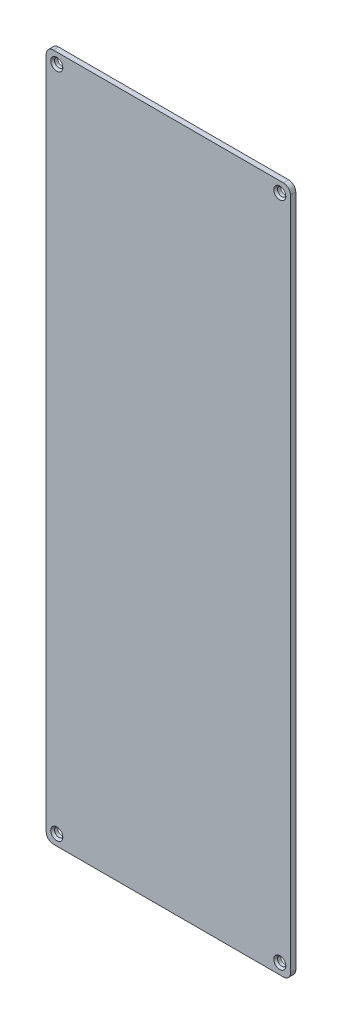
SolidWorks part; units mm, degrees
ref_plane "Front Plane" through (0, 0, 0) normal (0, 0, 1) x (1, 0, 0)
ref_plane "Top Plane" through (0, 0, 0) normal (0, 1, 0) x (1, 0, 0)
ref_plane "Right Plane" through (0, 0, 0) normal (1, 0, 0) x (0, 0, -1)
sketch "Sketch1" plane through (0, 0, 0) normal (0, 0, 1) x (1, 0, 0)
  line L0 (-1.3375, 127.642) -> (-1.3375, 0)
  line L1 (43.6165, 128.9795) -> (0, 128.9795)
  line L2 (44.954, 0) -> (44.954, 127.642)
  line L3 (0, -1.3375) -> (43.6165, -1.3375)
  line L4 (0, 0) -> (43.6165, 0) construction
  line L5 (43.6165, 0) -> (43.6165, 127.642) construction
  line L6 (43.6165, 127.642) -> (0, 127.642) construction
  line L7 (0, 127.642) -> (0, 0) construction
  arc A0 (0, 128.9795) -> (-1.3375, 127.642) centre (0, 127.642) ccw
  arc A1 (44.954, 127.642) -> (43.6165, 128.9795) centre (43.6165, 127.642) ccw
  arc A2 (43.6165, -1.3375) -> (44.954, 0) centre (43.6165, 0) ccw
  arc A3 (-1.3375, 0) -> (0, -1.3375) centre (0, 0) ccw
  circle A4 centre (43.6165, 0) radius 0.9 construction
  circle A5 centre (0, 0) radius 0.9 construction
  circle A6 centre (43.6165, 127.642) radius 0.9 construction
  circle A7 centre (0, 127.642) radius 0.9 construction
  point P2 (0, 0)
  dimension "D5" = 1.8
  dimension "D3" = 1.3375
  dimension "D1" = 46.2915
  dimension "D2" = 130.317
extrude "Boss-Extrude1" add sketch "Sketch1" along normal blind 1
hole_wizard "CSK for #0 Flat Head Machine Screw1" positions "Sketch6" profile "Sketch4" countersink size "#0" standard "ANSI Inch" end condition up to next
sketch "Sketch6" plane through (0, 0, 1) normal (0, 0, 1) x (1, 0, 0)
  line L0 (-1.3375, 127.642) -> (-1.3375, 0) construction
  line L1 (43.6165, 128.9795) -> (0, 128.9795) construction
  line L2 (0.6625, 126.9795) -> (42.922, 126.9795) construction
  line L3 (42.922, 126.9795) -> (42.922, 0.6945) construction
  line L4 (42.922, 0.6945) -> (0.6625, 0.6945) construction
  line L5 (0.6625, 0.6945) -> (0.6625, 126.9795) construction
  line L6 (44.954, 0) -> (44.954, 127.642) construction
  line L8 (0, -1.3375) -> (43.6165, -1.3375) construction
  point P3 (42.922, 126.9795)
  point P6 (0.6625, 0.6945)
  point P9 (42.922, 0.6945)
  point P15 (0.6625, 126.9795)
  point P41 (5.1852, 0.6945)
  point P42 (0.6625, 0.6945)
  point P43 (0.6625, 0.6945)
  dimension "D1" = 2
  dimension "D2" = 2
  dimension "D3" = 2.032
  dimension "D4" = 2.032
sketch "Sketch4" plane through (42.922, 126.9795, 1) normal (1, 0, 0) x (0, -1, 0)
  line L0 (0, 0) -> (0, 1)
  line L1 (0, 1) -> (0.8064, 1)
  line L2 (0.8064, 1) -> (0.8064, 0.3872)
  line L3 (0.8064, 0.3872) -> (1.143, 0)
  line L5 (1.143, 0) -> (0, 0)
  line L6 (-0.8065, 0.3872) -> (-1.143, 0) construction
  line L11 (0, -6.35) -> (0, 107.95) construction
  dimension "Thru Hole Dia." = 1.6129
  dimension "Thru Hole Depth" = 1
  dimension "Near C'Sink Dia." = 2.286
  dimension "Near C'Sink Angle" = 82
